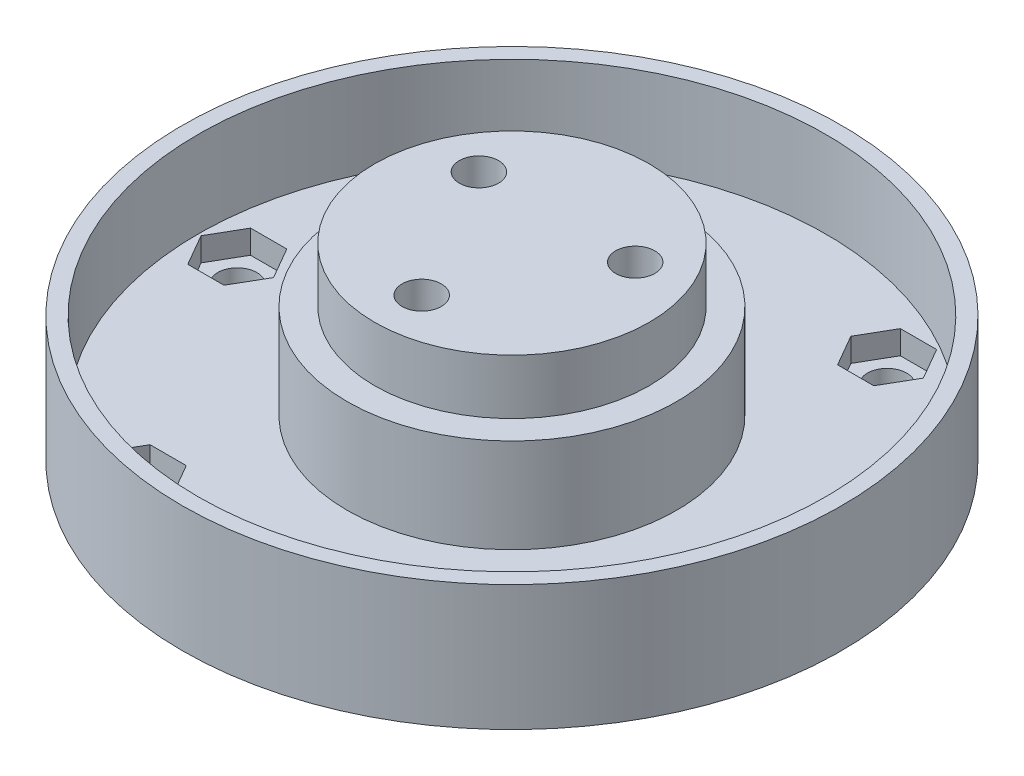
SolidWorks part; units mm, degrees
ref_plane "Front Plane" through (0, 0, 0) normal (0, 0, 1) x (1, 0, 0)
ref_plane "Top Plane" through (0, 0, 0) normal (0, 1, 0) x (1, 0, 0)
ref_plane "Right Plane" through (0, 0, 0) normal (1, 0, 0) x (0, 0, -1)
sketch "Sketch1" plane through (0, 0, 0) normal (0, 1, 0) x (1, 0, 0)
  line L0 (0, 0) -> (0, -11.5) construction
  line L1 (0, 0) -> (9.9593, 5.75) construction
  line L2 (0, 0) -> (-9.9593, 5.75) construction
  circle A0 centre (0, 0) radius 42
  circle A1 centre (0, 0) radius 21
  circle A2 centre (0, 0) radius 17.5
  circle A3 centre (0, 0) radius 40
  circle A4 centre (-9.9593, 5.75) radius 2.5
  circle A5 centre (9.9593, 5.75) radius 2.5
  circle A6 centre (0, -11.5) radius 2.5
  dimension "D1" = 35
  dimension "D2" = 42
  dimension "D3" = 2
  dimension "D6" = 5
  dimension "D8" = 80
  dimension "D4" = 120
  dimension "D5" = 120
  dimension "D7" = 11.5
extrude "Boss-Extrude1" add sketch "Sketch1" along normal blind 24 contours A2 region at (0, 0, 0)
extrude "Boss-Extrude2" add sketch "Sketch1<3>" along normal blind 17 contours A1 A2 region at (-20.406, 0, 0)
sketch "Sketch1<3>" plane through (0, 0, 0) normal (0, 1, 0) x (1, 0, 0) same geometry as "Sketch1"
extrude "Boss-Extrude4" add sketch "Sketch1<6>" along normal blind 5 contours A3 A1 region at (-38.8686, 0, 0)
sketch "Sketch1<6>" plane through (0, 0, 0) normal (0, 1, 0) x (1, 0, 0) same geometry as "Sketch1"
extrude "Boss-Extrude5" add sketch "Sketch1<7>" along normal blind 16 contours A0 A3 region at (-40.8121, 0, 0)
sketch "Sketch1<7>" plane through (0, 0, 0) normal (0, 1, 0) x (1, 0, 0) same geometry as "Sketch1"
sketch "Sketch2" plane through (0, 5, 0) normal (0, 1, 0) x (1, 0, 0)
  line L0 (0, 0) -> (-42, 0) construction
  circle A0 centre (0, 0) radius 30 construction
  circle A1 centre (0, 0) radius 35 construction
  circle A2 centre (-35, 0) radius 2.5
  circle A3 centre (-17.5, 30.3109) radius 2.5
  circle A4 centre (0, 0) radius 42 construction
  circle A5 centre (17.5, 30.3109) radius 2.5
  circle A6 centre (35, 0) radius 2.5
  circle A7 centre (17.5, -30.3109) radius 2.5
  circle A8 centre (-17.5, -30.3109) radius 2.5
  point P22 (0, 0)
  dimension "D1" = 60
  dimension "D2" = 5
  dimension "D3" = 5
  dimension "D4" = 6
extrude "Cut-Extrude1" cut sketch "Sketch2" against normal through all
sketch "Sketch3" plane through (0, 5, 0) normal (0, 1, 0) x (1, 0, 0)
  line L0 (0, 0) -> (0, 42) construction
  line L1 (-12.8812, 30.3109) -> (-15.1906, 34.3109)
  line L2 (-15.1906, 34.3109) -> (-19.8094, 34.3109)
  line L3 (-19.8094, 34.3109) -> (-22.1188, 30.3109)
  line L4 (-22.1188, 30.3109) -> (-19.8094, 26.3109)
  line L5 (-19.8094, 26.3109) -> (-15.1906, 26.3109)
  line L6 (-15.1906, 26.3109) -> (-12.8812, 30.3109)
  line L7 (0, 0) -> (36.3731, 21) construction
  line L8 (19.8094, 26.3109) -> (22.1188, 30.3109)
  line L9 (22.1188, 30.3109) -> (19.8094, 34.3109)
  line L10 (19.8094, 34.3109) -> (15.1906, 34.3109)
  line L11 (15.1906, 34.3109) -> (12.8812, 30.3109)
  line L12 (12.8812, 30.3109) -> (15.1906, 26.3109)
  line L13 (15.1906, 26.3109) -> (19.8094, 26.3109)
  line L14 (0, 0) -> (36.3731, -21) construction
  line L15 (32.6906, -4) -> (37.3094, -4)
  line L16 (37.3094, -4) -> (39.6188, 0)
  line L17 (39.6188, 0) -> (37.3094, 4)
  line L18 (37.3094, 4) -> (32.6906, 4)
  line L19 (32.6906, 4) -> (30.3812, 0)
  line L20 (30.3812, 0) -> (32.6906, -4)
  line L21 (0, 0) -> (0, -42) construction
  line L22 (12.8812, -30.3109) -> (15.1906, -34.3109)
  line L23 (15.1906, -34.3109) -> (19.8094, -34.3109)
  line L24 (19.8094, -34.3109) -> (22.1188, -30.3109)
  line L25 (22.1188, -30.3109) -> (19.8094, -26.3109)
  line L26 (19.8094, -26.3109) -> (15.1906, -26.3109)
  line L27 (15.1906, -26.3109) -> (12.8812, -30.3109)
  line L28 (0, 0) -> (-36.3731, -21) construction
  line L29 (-19.8094, -26.3109) -> (-22.1188, -30.3109)
  line L30 (-22.1188, -30.3109) -> (-19.8094, -34.3109)
  line L31 (-19.8094, -34.3109) -> (-15.1906, -34.3109)
  line L32 (-15.1906, -34.3109) -> (-12.8812, -30.3109)
  line L33 (-12.8812, -30.3109) -> (-15.1906, -26.3109)
  line L34 (-15.1906, -26.3109) -> (-19.8094, -26.3109)
  line L35 (0, 0) -> (-36.3731, 21) construction
  line L36 (-32.6906, 4) -> (-37.3094, 4)
  line L37 (-37.3094, 4) -> (-39.6188, 0)
  line L38 (-39.6188, 0) -> (-37.3094, -4)
  line L39 (-37.3094, -4) -> (-32.6906, -4)
  line L40 (-32.6906, -4) -> (-30.3812, 0)
  line L41 (-30.3812, 0) -> (-32.6906, 4)
  circle A0 centre (-17.5, 30.3109) radius 4 construction
  circle A1 centre (0, 0) radius 42 construction
  point P51 (0, 0)
  dimension "D1" = 8
  dimension "D2" = 6
extrude "Cut-Extrude2" cut sketch "Sketch3" against normal blind 3
sketch "Sketch4" plane through (0, 0, 0) normal (0, -1, 0) x (1, 0, 0)
  line L0 (0, 0) -> (15.3606, 0) construction
  line L1 (0, 6.8812) -> (4, 9.1906)
  line L2 (4, 9.1906) -> (4, 13.8094)
  line L3 (4, 13.8094) -> (0, 16.1188)
  line L4 (0, 16.1188) -> (-4, 13.8094)
  line L5 (-4, 13.8094) -> (-4, 9.1906)
  line L6 (-4, 9.1906) -> (0, 6.8812)
  line L7 (0, 0) -> (-7.6803, -13.3027) construction
  line L8 (5.9593, -3.4406) -> (5.9593, -8.0594)
  line L9 (9.9593, -1.1312) -> (5.9593, -3.4406)
  line L10 (13.9593, -3.4406) -> (9.9593, -1.1312)
  line L11 (13.9593, -8.0594) -> (13.9593, -3.4406)
  line L12 (9.9593, -10.3688) -> (13.9593, -8.0594)
  line L13 (5.9593, -8.0594) -> (9.9593, -10.3688)
  line L14 (0, 0) -> (-7.6803, 13.3027) construction
  line L15 (-5.9593, -3.4406) -> (-9.9593, -1.1312)
  line L16 (-5.9593, -8.0594) -> (-5.9593, -3.4406)
  line L17 (-9.9593, -10.3688) -> (-5.9593, -8.0594)
  line L18 (-13.9593, -8.0594) -> (-9.9593, -10.3688)
  line L19 (-13.9593, -3.4406) -> (-13.9593, -8.0594)
  line L20 (-9.9593, -1.1312) -> (-13.9593, -3.4406)
  circle A0 centre (0, 11.5) radius 4 construction
  point P29 (0, 0)
  dimension "D1" = 8
  dimension "D2" = 3
extrude "Cut-Extrude3" cut sketch "Sketch4" against normal blind 20
